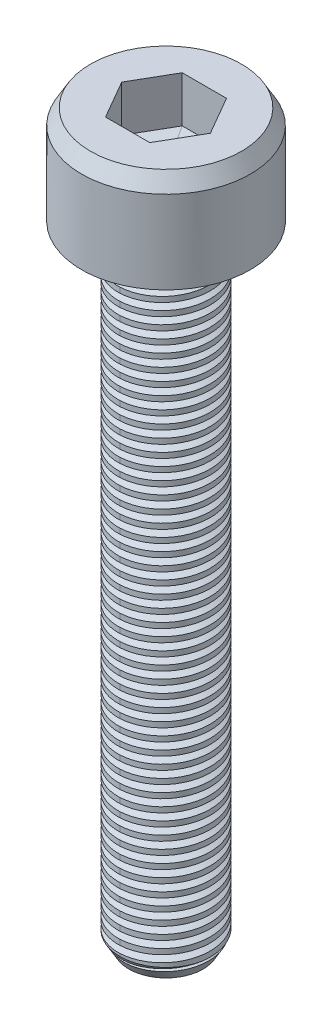
SolidWorks part; units mm, degrees
ref_plane "Front Plane" through (0, 0, 0) normal (0, 0, 1) x (1, 0, 0)
ref_plane "Top Plane" through (0, 0, 0) normal (0, 1, 0) x (1, 0, 0)
ref_plane "Right Plane" through (0, 0, 0) normal (1, 0, 0) x (0, 0, -1)
sketch "Sketch1" plane through (0, 0, 0) normal (0, 1, 0) x (1, 0, 0)
  circle A0 centre (0, 0) radius 2.75
  dimension "D1" = 5.5
extrude "Boss-Extrude1" add sketch "Sketch1" along normal blind 2.7
sketch "Sketch2" plane through (0, 2.7, 0) normal (0, 1, 0) x (1, 0, 0)
  circle A0 centre (0, 0) radius 2.75
  circle A1 centre (0, 0) radius 2.75 construction
  dimension "D1" = 5.5
extrude "Boss-Extrude2" add sketch "Sketch2" along normal blind 0.5 draft 30
sketch "Sketch5" plane through (0, 3.2, 0) normal (0, 1, 0) x (1, 0, 0)
  line L1 (1.4434, 0) -> (0.7217, 1.25)
  line L2 (0.7217, 1.25) -> (-0.7217, 1.25)
  line L3 (-0.7217, 1.25) -> (-1.4434, 0)
  line L4 (-1.4434, 0) -> (-0.7217, -1.25)
  line L5 (-0.7217, -1.25) -> (0.7217, -1.25)
  line L6 (0.7217, -1.25) -> (1.4434, 0)
  circle A0 centre (0, 0) radius 1.25 construction
  circle A1 centre (0, 0) radius 2.4613 construction
  dimension "D1" = 2.5
extrude "Cut-Extrude3" cut sketch "Sketch5" against normal blind 1.5
sketch "Sketch6" plane through (0, 1.7, 0) normal (0, 1, 0) x (1, 0, 0)
  line L0 (1.4434, 0) -> (0.7217, 1.25) construction
  line L1 (1.4434, 0) -> (0.7217, 1.25)
  line L2 (0.7217, 1.25) -> (-0.7217, 1.25)
  line L3 (-0.7217, 1.25) -> (-1.4434, 0)
  line L4 (-1.4434, 0) -> (-0.7217, -1.25)
  line L5 (-0.7217, -1.25) -> (0.7217, -1.25)
  line L6 (0.7217, -1.25) -> (1.4434, 0)
  circle A0 centre (0, 0) radius 1.25 construction
extrude "Cut-Extrude4" cut sketch "Sketch6" against normal blind 0.25 draft 80
sketch "Sketch7" plane through (0, 0, 0) normal (0, -1, 0) x (1, 0, 0)
  circle A0 centre (0, 0) radius 1.5
  circle A1 centre (0, 0) radius 2.75 construction
  dimension "D1" = 3
extrude "Boss-Extrude3" add sketch "Sketch7" along normal blind 20 contours A0
sketch "Sketch8" plane through (0, -20, 0) normal (0, -1, 0) x (1, 0, 0)
  circle A0 centre (0, 0) radius 1.5
  circle A1 centre (0, 0) radius 1.5 construction
  dimension "D1" = 3
extrude "Boss-Extrude4" add sketch "Sketch8" along normal blind 0.5 draft 30
sketch "Sketch9" plane through (0, -20.5, 0) normal (0, -1, 0) x (1, 0, 0)
  circle A0 centre (0, 0) radius 1.5
  circle A1 centre (0, 0) radius 1.2113 construction
  dimension "D1" = 3
curve "Helix/Spiral1" pitch 0.4 height 20 radius 1.5 centre (0, -20.5, 0) axis (0, 1, 0) start towards (1, 0, 0)
sketch "Sketch10" plane through (0, 0, 0) normal (0, 0, 1) x (1, 0, 0)
  line L1 (1.3037, -20.5) -> (1.5981, -20.67)
  line L2 (1.5981, -20.67) -> (1.5981, -20.33)
  line L3 (1.5981, -20.33) -> (1.3037, -20.5)
  circle A0 centre (1.5, -20.5) radius 0.0981 construction
  spline S0 degree 3 poles (1.5, -20.5) (1.5, -20.4917) (1.4219, -20.475) (1.0883, -20.45) (0.589, -20.425) (0, -20.4) (-0.589, -20.375) (-1.0883, -20.35) (-1.4219, -20.325) (-1.5391, -20.3) (-1.4219, -20.275) (-1.0883, -20.25) (-0.589, -20.225) (0, -20.2) (0.589, -20.175) (1.0883, -20.15) (1.4219, -20.125) (1.5391, -20.1) (1.4219, -20.075) (1.0883, -20.05) (0.589, -20.025) (0, -20) (-0.589, -19.975) (-1.0883, -19.95) (-1.4219, -19.925) (-1.5391, -19.9) (-1.4219, -19.875) (-1.0883, -19.85) (-0.589, -19.825) (0, -19.8) (0.589, -19.775) (1.0883, -19.75) (1.4219, -19.725) (1.5391, -19.7) (1.4219, -19.675) (1.0883, -19.65) (0.589, -19.625) (0, -19.6) (-0.589, -19.575) (-1.0883, -19.55) (-1.4219, -19.525) (-1.5391, -19.5) (-1.4219, -19.475) (-1.0883, -19.45) (-0.589, -19.425) (0, -19.4) (0.589, -19.375) (1.0883, -19.35) (1.4219, -19.325) (1.5391, -19.3) (1.4219, -19.275) (1.0883, -19.25) (0.589, -19.225) (0, -19.2) (-0.589, -19.175) (-1.0883, -19.15) (-1.4219, -19.125) (-1.5391, -19.1) (-1.4219, -19.075) (-1.0883, -19.05) (-0.589, -19.025) (0, -19) (0.589, -18.975) (1.0883, -18.95) (1.4219, -18.925) (1.5391, -18.9) (1.4219, -18.875) (1.0883, -18.85) (0.589, -18.825) (0, -18.8) (-0.589, -18.775) (-1.0883, -18.75) (-1.4219, -18.725) (-1.5391, -18.7) (-1.4219, -18.675) (-1.0883, -18.65) (-0.589, -18.625) (0, -18.6) (0.589, -18.575) (1.0883, -18.55) (1.4219, -18.525) (1.5391, -18.5) (1.4219, -18.475) (1.0883, -18.45) (0.589, -18.425) (0, -18.4) (-0.589, -18.375) (-1.0883, -18.35) (-1.4219, -18.325) (-1.5391, -18.3) (-1.4219, -18.275) (-1.0883, -18.25) (-0.589, -18.225) (0, -18.2) (0.589, -18.175) (1.0883, -18.15) (1.4219, -18.125) (1.5391, -18.1) (1.4219, -18.075) (1.0883, -18.05) (0.589, -18.025) (0, -18) (-0.589, -17.975) (-1.0883, -17.95) (-1.4219, -17.925) (-1.5391, -17.9) (-1.4219, -17.875) (-1.0883, -17.85) (-0.589, -17.825) (0, -17.8) (0.589, -17.775) (1.0883, -17.75) (1.4219, -17.725) (1.5391, -17.7) (1.4219, -17.675) (1.0883, -17.65) (0.589, -17.625) (0, -17.6) (-0.589, -17.575) (-1.0883, -17.55) (-1.4219, -17.525) (-1.5391, -17.5) (-1.4219, -17.475) (-1.0883, -17.45) (-0.589, -17.425) (0, -17.4) (0.589, -17.375) (1.0883, -17.35) (1.4219, -17.325) (1.5391, -17.3) (1.4219, -17.275) (1.0883, -17.25) (0.589, -17.225) (0, -17.2) (-0.589, -17.175) (-1.0883, -17.15) (-1.4219, -17.125) (-1.5391, -17.1) (-1.4219, -17.075) (-1.0883, -17.05) (-0.589, -17.025) (0, -17) (0.589, -16.975) (1.0883, -16.95) (1.4219, -16.925) (1.5391, -16.9) (1.4219, -16.875) (1.0883, -16.85) (0.589, -16.825) (0, -16.8) (-0.589, -16.775) (-1.0883, -16.75) (-1.4219, -16.725) (-1.5391, -16.7) (-1.4219, -16.675) (-1.0883, -16.65) (-0.589, -16.625) (0, -16.6) (0.589, -16.575) (1.0883, -16.55) (1.4219, -16.525) (1.5391, -16.5) (1.4219, -16.475) (1.0883, -16.45) (0.589, -16.425) (0, -16.4) (-0.589, -16.375) (-1.0883, -16.35) (-1.4219, -16.325) (-1.5391, -16.3) (-1.4219, -16.275) (-1.0883, -16.25) (-0.589, -16.225) (0, -16.2) (0.589, -16.175) (1.0883, -16.15) (1.4219, -16.125) (1.5391, -16.1) (1.4219, -16.075) (1.0883, -16.05) (0.589, -16.025) (0, -16) (-0.589, -15.975) (-1.0883, -15.95) (-1.4219, -15.925) (-1.5391, -15.9) (-1.4219, -15.875) (-1.0883, -15.85) (-0.589, -15.825) (0, -15.8) (0.589, -15.775) (1.0883, -15.75) (1.4219, -15.725) (1.5391, -15.7) (1.4219, -15.675) (1.0883, -15.65) (0.589, -15.625) (0, -15.6) (-0.589, -15.575) (-1.0883, -15.55) (-1.4219, -15.525) (-1.5391, -15.5) (-1.4219, -15.475) (-1.0883, -15.45) (-0.589, -15.425) (0, -15.4) (0.589, -15.375) (1.0883, -15.35) (1.4219, -15.325) (1.5391, -15.3) (1.4219, -15.275) (1.0883, -15.25) (0.589, -15.225) (0, -15.2) (-0.589, -15.175) (-1.0883, -15.15) (-1.4219, -15.125) (-1.5391, -15.1) (-1.4219, -15.075) (-1.0883, -15.05) (-0.589, -15.025) (0, -15) (0.589, -14.975) (1.0883, -14.95) (1.4219, -14.925) (1.5391, -14.9) (1.4219, -14.875) (1.0883, -14.85) (0.589, -14.825) (0, -14.8) (-0.589, -14.775) (-1.0883, -14.75) (-1.4219, -14.725) (-1.5391, -14.7) (-1.4219, -14.675) (-1.0883, -14.65) (-0.589, -14.625) (0, -14.6) (0.589, -14.575) (1.0883, -14.55) (1.4219, -14.525) (1.5391, -14.5) (1.4219, -14.475) (1.0883, -14.45) (0.589, -14.425) (0, -14.4) (-0.589, -14.375) (-1.0883, -14.35) (-1.4219, -14.325) (-1.5391, -14.3) (-1.4219, -14.275) (-1.0883, -14.25) (-0.589, -14.225) (0, -14.2) (0.589, -14.175) (1.0883, -14.15) (1.4219, -14.125) (1.5391, -14.1) (1.4219, -14.075) (1.0883, -14.05) (0.589, -14.025) (0, -14) (-0.589, -13.975) (-1.0883, -13.95) (-1.4219, -13.925) (-1.5391, -13.9) (-1.4219, -13.875) (-1.0883, -13.85) (-0.589, -13.825) (0, -13.8) (0.589, -13.775) (1.0883, -13.75) (1.4219, -13.725) (1.5391, -13.7) (1.4219, -13.675) (1.0883, -13.65) (0.589, -13.625) (0, -13.6) (-0.589, -13.575) (-1.0883, -13.55) (-1.4219, -13.525) (-1.5391, -13.5) (-1.4219, -13.475) (-1.0883, -13.45) (-0.589, -13.425) (0, -13.4) (0.589, -13.375) (1.0883, -13.35) (1.4219, -13.325) (1.5391, -13.3) (1.4219, -13.275) (1.0883, -13.25) (0.589, -13.225) (0, -13.2) (-0.589, -13.175) (-1.0883, -13.15) (-1.4219, -13.125) (-1.5391, -13.1) (-1.4219, -13.075) (-1.0883, -13.05) (-0.589, -13.025) (0, -13) (0.589, -12.975) (1.0883, -12.95) (1.4219, -12.925) (1.5391, -12.9) (1.4219, -12.875) (1.0883, -12.85) (0.589, -12.825) (0, -12.8) (-0.589, -12.775) (-1.0883, -12.75) (-1.4219, -12.725) (-1.5391, -12.7) (-1.4219, -12.675) (-1.0883, -12.65) (-0.589, -12.625) (0, -12.6) (0.589, -12.575) (1.0883, -12.55) (1.4219, -12.525) (1.5391, -12.5) (1.4219, -12.475) (1.0883, -12.45) (0.589, -12.425) (0, -12.4) (-0.589, -12.375) (-1.0883, -12.35) (-1.4219, -12.325) (-1.5391, -12.3) (-1.4219, -12.275) (-1.0883, -12.25) (-0.589, -12.225) (0, -12.2) (0.589, -12.175) (1.0883, -12.15) (1.4219, -12.125) (1.5391, -12.1) (1.4219, -12.075) (1.0883, -12.05) (0.589, -12.025) (0, -12) (-0.589, -11.975) (-1.0883, -11.95) (-1.4219, -11.925) (-1.5391, -11.9) (-1.4219, -11.875) (-1.0883, -11.85) (-0.589, -11.825) (0, -11.8) (0.589, -11.775) (1.0883, -11.75) (1.4219, -11.725) (1.5391, -11.7) (1.4219, -11.675) (1.0883, -11.65) (0.589, -11.625) (0, -11.6) (-0.589, -11.575) (-1.0883, -11.55) (-1.4219, -11.525) (-1.5391, -11.5) (-1.4219, -11.475) (-1.0883, -11.45) (-0.589, -11.425) (0, -11.4) (0.589, -11.375) (1.0883, -11.35) (1.4219, -11.325) (1.5391, -11.3) (1.4219, -11.275) (1.0883, -11.25) (0.589, -11.225) (0, -11.2) (-0.589, -11.175) (-1.0883, -11.15) (-1.4219, -11.125) (-1.5391, -11.1) (-1.4219, -11.075) (-1.0883, -11.05) (-0.589, -11.025) (0, -11) (0.589, -10.975) (1.0883, -10.95) (1.4219, -10.925) (1.5391, -10.9) (1.4219, -10.875) (1.0883, -10.85) (0.589, -10.825) (0, -10.8) (-0.589, -10.775) (-1.0883, -10.75) (-1.4219, -10.725) (-1.5391, -10.7) (-1.4219, -10.675) (-1.0883, -10.65) (-0.589, -10.625) (0, -10.6) (0.589, -10.575) (1.0883, -10.55) (1.4219, -10.525) (1.5391, -10.5) (1.4219, -10.475) (1.0883, -10.45) (0.589, -10.425) (0, -10.4) (-0.589, -10.375) (-1.0883, -10.35) (-1.4219, -10.325) (-1.5391, -10.3) (-1.4219, -10.275) (-1.0883, -10.25) (-0.589, -10.225) (0, -10.2) (0.589, -10.175) (1.0883, -10.15) (1.4219, -10.125) (1.5391, -10.1) (1.4219, -10.075) (1.0883, -10.05) (0.589, -10.025) (0, -10) (-0.589, -9.975) (-1.0883, -9.95) (-1.4219, -9.925) (-1.5391, -9.9) (-1.4219, -9.875) (-1.0883, -9.85) (-0.589, -9.825) (0, -9.8) (0.589, -9.775) (1.0883, -9.75) (1.4219, -9.725) (1.5391, -9.7) (1.4219, -9.675) (1.0883, -9.65) (0.589, -9.625) (0, -9.6) (-0.589, -9.575) (-1.0883, -9.55) (-1.4219, -9.525) (-1.5391, -9.5) (-1.4219, -9.475) (-1.0883, -9.45) (-0.589, -9.425) (0, -9.4) (0.589, -9.375) (1.0883, -9.35) (1.4219, -9.325) (1.5391, -9.3) (1.4219, -9.275) (1.0883, -9.25) (0.589, -9.225) (0, -9.2) (-0.589, -9.175) (-1.0883, -9.15) (-1.4219, -9.125) (-1.5391, -9.1) (-1.4219, -9.075) (-1.0883, -9.05) (-0.589, -9.025) (0, -9) (0.589, -8.975) (1.0883, -8.95) (1.4219, -8.925) (1.5391, -8.9) (1.4219, -8.875) (1.0883, -8.85) (0.589, -8.825) (0, -8.8) (-0.589, -8.775) (-1.0883, -8.75) (-1.4219, -8.725) (-1.5391, -8.7) (-1.4219, -8.675) (-1.0883, -8.65) (-0.589, -8.625) (0, -8.6) (0.589, -8.575) (1.0883, -8.55) (1.4219, -8.525) (1.5391, -8.5) (1.4219, -8.475) (1.0883, -8.45) (0.589, -8.425) (0, -8.4) (-0.589, -8.375) (-1.0883, -8.35) (-1.4219, -8.325) (-1.5391, -8.3) (-1.4219, -8.275) (-1.0883, -8.25) (-0.589, -8.225) (0, -8.2) (0.589, -8.175) (1.0883, -8.15) (1.4219, -8.125) (1.5391, -8.1) (1.4219, -8.075) (1.0883, -8.05) (0.589, -8.025) (0, -8) (-0.589, -7.975) (-1.0883, -7.95) (-1.4219, -7.925) (-1.5391, -7.9) (-1.4219, -7.875) (-1.0883, -7.85) (-0.589, -7.825) (0, -7.8) (0.589, -7.775) (1.0883, -7.75) (1.4219, -7.725) (1.5391, -7.7) (1.4219, -7.675) (1.0883, -7.65) (0.589, -7.625) (0, -7.6) (-0.589, -7.575) (-1.0883, -7.55) (-1.4219, -7.525) (-1.5391, -7.5) (-1.4219, -7.475) (-1.0883, -7.45) (-0.589, -7.425) (0, -7.4) (0.589, -7.375) (1.0883, -7.35) (1.4219, -7.325) (1.5391, -7.3) (1.4219, -7.275) (1.0883, -7.25) (0.589, -7.225) (0, -7.2) (-0.589, -7.175) (-1.0883, -7.15) (-1.4219, -7.125) (-1.5391, -7.1) (-1.4219, -7.075) (-1.0883, -7.05) (-0.589, -7.025) (0, -7) (0.589, -6.975) (1.0883, -6.95) (1.4219, -6.925) (1.5391, -6.9) (1.4219, -6.875) (1.0883, -6.85) (0.589, -6.825) (0, -6.8) (-0.589, -6.775) (-1.0883, -6.75) (-1.4219, -6.725) (-1.5391, -6.7) (-1.4219, -6.675) (-1.0883, -6.65) (-0.589, -6.625) (0, -6.6) (0.589, -6.575) (1.0883, -6.55) (1.4219, -6.525) (1.5391, -6.5) (1.4219, -6.475) (1.0883, -6.45) (0.589, -6.425) (0, -6.4) (-0.589, -6.375) (-1.0883, -6.35) (-1.4219, -6.325) (-1.5391, -6.3) (-1.4219, -6.275) (-1.0883, -6.25) (-0.589, -6.225) (0, -6.2) (0.589, -6.175) (1.0883, -6.15) (1.4219, -6.125) (1.5391, -6.1) (1.4219, -6.075) (1.0883, -6.05) (0.589, -6.025) (0, -6) (-0.589, -5.975) (-1.0883, -5.95) (-1.4219, -5.925) (-1.5391, -5.9) (-1.4219, -5.875) (-1.0883, -5.85) (-0.589, -5.825) (0, -5.8) (0.589, -5.775) (1.0883, -5.75) (1.4219, -5.725) (1.5391, -5.7) (1.4219, -5.675) (1.0883, -5.65) (0.589, -5.625) (0, -5.6) (-0.589, -5.575) (-1.0883, -5.55) (-1.4219, -5.525) (-1.5391, -5.5) (-1.4219, -5.475) (-1.0883, -5.45) (-0.589, -5.425) (0, -5.4) (0.589, -5.375) (1.0883, -5.35) (1.4219, -5.325) (1.5391, -5.3) (1.4219, -5.275) (1.0883, -5.25) (0.589, -5.225) (0, -5.2) (-0.589, -5.175) (-1.0883, -5.15) (-1.4219, -5.125) (-1.5391, -5.1) (-1.4219, -5.075) (-1.0883, -5.05) (-0.589, -5.025) (0, -5) (0.589, -4.975) (1.0883, -4.95) (1.4219, -4.925) (1.5391, -4.9) (1.4219, -4.875) (1.0883, -4.85) (0.589, -4.825) (0, -4.8) (-0.589, -4.775) (-1.0883, -4.75) (-1.4219, -4.725) (-1.5391, -4.7) (-1.4219, -4.675) (-1.0883, -4.65) (-0.589, -4.625) (0, -4.6) (0.589, -4.575) (1.0883, -4.55) (1.4219, -4.525) (1.5391, -4.5) (1.4219, -4.475) (1.0883, -4.45) (0.589, -4.425) (0, -4.4) (-0.589, -4.375) (-1.0883, -4.35) (-1.4219, -4.325) (-1.5391, -4.3) (-1.4219, -4.275) (-1.0883, -4.25) (-0.589, -4.225) (0, -4.2) (0.589, -4.175) (1.0883, -4.15) (1.4219, -4.125) (1.5391, -4.1) (1.4219, -4.075) (1.0883, -4.05) (0.589, -4.025) (0, -4) (-0.589, -3.975) (-1.0883, -3.95) (-1.4219, -3.925) (-1.5391, -3.9) (-1.4219, -3.875) (-1.0883, -3.85) (-0.589, -3.825) (0, -3.8) (0.589, -3.775) (1.0883, -3.75) (1.4219, -3.725) (1.5391, -3.7) (1.4219, -3.675) (1.0883, -3.65) (0.589, -3.625) (0, -3.6) (-0.589, -3.575) (-1.0883, -3.55) (-1.4219, -3.525) (-1.5391, -3.5) (-1.4219, -3.475) (-1.0883, -3.45) (-0.589, -3.425) (0, -3.4) (0.589, -3.375) (1.0883, -3.35) (1.4219, -3.325) (1.5391, -3.3) (1.4219, -3.275) (1.0883, -3.25) (0.589, -3.225) (0, -3.2) (-0.589, -3.175) (-1.0883, -3.15) (-1.4219, -3.125) (-1.5391, -3.1) (-1.4219, -3.075) (-1.0883, -3.05) (-0.589, -3.025) (0, -3) (0.589, -2.975) (1.0883, -2.95) (1.4219, -2.925) (1.5391, -2.9) (1.4219, -2.875) (1.0883, -2.85) (0.589, -2.825) (0, -2.8) (-0.589, -2.775) (-1.0883, -2.75) (-1.4219, -2.725) (-1.5391, -2.7) (-1.4219, -2.675) (-1.0883, -2.65) (-0.589, -2.625) (0, -2.6) (0.589, -2.575) (1.0883, -2.55) (1.4219, -2.525) (1.5391, -2.5) (1.4219, -2.475) (1.0883, -2.45) (0.589, -2.425) (0, -2.4) (-0.589, -2.375) (-1.0883, -2.35) (-1.4219, -2.325) (-1.5391, -2.3) (-1.4219, -2.275) (-1.0883, -2.25) (-0.589, -2.225) (0, -2.2) (0.589, -2.175) (1.0883, -2.15) (1.4219, -2.125) (1.5391, -2.1) (1.4219, -2.075) (1.0883, -2.05) (0.589, -2.025) (0, -2) (-0.589, -1.975) (-1.0883, -1.95) (-1.4219, -1.925) (-1.5391, -1.9) (-1.4219, -1.875) (-1.0883, -1.85) (-0.589, -1.825) (0, -1.8) (0.589, -1.775) (1.0883, -1.75) (1.4219, -1.725) (1.5391, -1.7) (1.4219, -1.675) (1.0883, -1.65) (0.589, -1.625) (0, -1.6) (-0.589, -1.575) (-1.0883, -1.55) (-1.4219, -1.525) (-1.5391, -1.5) (-1.4219, -1.475) (-1.0883, -1.45) (-0.589, -1.425) (0, -1.4) (0.589, -1.375) (1.0883, -1.35) (1.4219, -1.325) (1.5391, -1.3) (1.4219, -1.275) (1.0883, -1.25) (0.589, -1.225) (0, -1.2) (-0.589, -1.175) (-1.0883, -1.15) (-1.4219, -1.125) (-1.5391, -1.1) (-1.4219, -1.075) (-1.0883, -1.05) (-0.589, -1.025) (0, -1) (0.589, -0.975) (1.0883, -0.95) (1.4219, -0.925) (1.5391, -0.9) (1.4219, -0.875) (1.0883, -0.85) (0.589, -0.825) (0, -0.8) (-0.589, -0.775) (-1.0883, -0.75) (-1.4219, -0.725) (-1.5391, -0.7) (-1.4219, -0.675) (-1.0883, -0.65) (-0.589, -0.625) (0, -0.6) (0.589, -0.575) (1.0883, -0.55) (1.4219, -0.525) (1.5, -0.5083) (1.5, -0.5) knots 0 0 0 0 0.00125 0.0025 0.00375 0.005 0.00625 0.0075 0.00875 0.01 0.01125 0.0125 0.01375 0.015 0.01625 0.0175 0.01875 0.02 0.02125 0.0225 0.02375 0.025 0.02625 0.0275 0.02875 0.03 0.03125 0.0325 0.03375 0.035 0.03625 0.0375 0.03875 0.04 0.04125 0.0425 0.04375 0.045 0.04625 0.0475 0.04875 0.05 0.05125 0.0525 0.05375 0.055 0.05625 0.0575 0.05875 0.06 0.06125 0.0625 0.06375 0.065 0.06625 0.0675 0.06875 0.07 0.07125 0.0725 0.07375 0.075 0.07625 0.0775 0.07875 0.08 0.08125 0.0825 0.08375 0.085 0.08625 0.0875 0.08875 0.09 0.09125 0.0925 0.09375 0.095 0.09625 0.0975 0.09875 0.1 0.10125 0.1025 0.10375 0.105 0.10625 0.1075 0.10875 0.11 0.11125 0.1125 0.11375 0.115 0.11625 0.1175 0.11875 0.12 0.12125 0.1225 0.12375 0.125 0.12625 0.1275 0.12875 0.13 0.13125 0.1325 0.13375 0.135 0.13625 0.1375 0.13875 0.14 0.14125 0.1425 0.14375 0.145 0.14625 0.1475 0.14875 0.15 0.15125 0.1525 0.15375 0.155 0.15625 0.1575 0.15875 0.16 0.16125 0.1625 0.16375 0.165 0.16625 0.1675 0.16875 0.17 0.17125 0.1725 0.17375 0.175 0.17625 0.1775 0.17875 0.18 0.18125 0.1825 0.18375 0.185 0.18625 0.1875 0.18875 0.19 0.19125 0.1925 0.19375 0.195 0.19625 0.1975 0.19875 0.2 0.20125 0.2025 0.20375 0.205 0.20625 0.2075 0.20875 0.21 0.21125 0.2125 0.21375 0.215 0.21625 0.2175 0.21875 0.22 0.22125 0.2225 0.22375 0.225 0.22625 0.2275 0.22875 0.23 0.23125 0.2325 0.23375 0.235 0.23625 0.2375 0.23875 0.24 0.24125 0.2425 0.24375 0.245 0.24625 0.2475 0.24875 0.25 0.25125 0.2525 0.25375 0.255 0.25625 0.2575 0.25875 0.26 0.26125 0.2625 0.26375 0.265 0.26625 0.2675 0.26875 0.27 0.27125 0.2725 0.27375 0.275 0.27625 0.2775 0.27875 0.28 0.28125 0.2825 0.28375 0.285 0.28625 0.2875 0.28875 0.29 0.29125 0.2925 0.29375 0.295 0.29625 0.2975 0.29875 0.3 0.30125 0.3025 0.30375 0.305 0.30625 0.3075 0.30875 0.31 0.31125 0.3125 0.31375 0.315 0.31625 0.3175 0.31875 0.32 0.32125 0.3225 0.32375 0.325 0.32625 0.3275 0.32875 0.33 0.33125 0.3325 0.33375 0.335 0.33625 0.3375 0.33875 0.34 0.34125 0.3425 0.34375 0.345 0.34625 0.3475 0.34875 0.35 0.35125 0.3525 0.35375 0.355 0.35625 0.3575 0.35875 0.36 0.36125 0.3625 0.36375 0.365 0.36625 0.3675 0.36875 0.37 0.37125 0.3725 0.37375 0.375 0.37625 0.3775 0.37875 0.38 0.38125 0.3825 0.38375 0.385 0.38625 0.3875 0.38875 0.39 0.39125 0.3925 0.39375 0.395 0.39625 0.3975 0.39875 0.4 0.40125 0.4025 0.40375 0.405 0.40625 0.4075 0.40875 0.41 0.41125 0.4125 0.41375 0.415 0.41625 0.4175 0.41875 0.42 0.42125 0.4225 0.42375 0.425 0.42625 0.4275 0.42875 0.43 0.43125 0.4325 0.43375 0.435 0.43625 0.4375 0.43875 0.44 0.44125 0.4425 0.44375 0.445 0.44625 0.4475 0.44875 0.45 0.45125 0.4525 0.45375 0.455 0.45625 0.4575 0.45875 0.46 0.46125 0.4625 0.46375 0.465 0.46625 0.4675 0.46875 0.47 0.47125 0.4725 0.47375 0.475 0.47625 0.4775 0.47875 0.48 0.48125 0.4825 0.48375 0.485 0.48625 0.4875 0.48875 0.49 0.49125 0.4925 0.49375 0.495 0.49625 0.4975 0.49875 0.5 0.50125 0.5025 0.50375 0.505 0.50625 0.5075 0.50875 0.51 0.51125 0.5125 0.51375 0.515 0.51625 0.5175 0.51875 0.52 0.52125 0.5225 0.52375 0.525 0.52625 0.5275 0.52875 0.53 0.53125 0.5325 0.53375 0.535 0.53625 0.5375 0.53875 0.54 0.54125 0.5425 0.54375 0.545 0.54625 0.5475 0.54875 0.55 0.55125 0.5525 0.55375 0.555 0.55625 0.5575 0.55875 0.56 0.56125 0.5625 0.56375 0.565 0.56625 0.5675 0.56875 0.57 0.57125 0.5725 0.57375 0.575 0.57625 0.5775 0.57875 0.58 0.58125 0.5825 0.58375 0.585 0.58625 0.5875 0.58875 0.59 0.59125 0.5925 0.59375 0.595 0.59625 0.5975 0.59875 0.6 0.60125 0.6025 0.60375 0.605 0.60625 0.6075 0.60875 0.61 0.61125 0.6125 0.61375 0.615 0.61625 0.6175 0.61875 0.62 0.62125 0.6225 0.62375 0.625 0.62625 0.6275 0.62875 0.63 0.63125 0.6325 0.63375 0.635 0.63625 0.6375 0.63875 0.64 0.64125 0.6425 0.64375 0.645 0.64625 0.6475 0.64875 0.65 0.65125 0.6525 0.65375 0.655 0.65625 0.6575 0.65875 0.66 0.66125 0.6625 0.66375 0.665 0.66625 0.6675 0.66875 0.67 0.67125 0.6725 0.67375 0.675 0.67625 0.6775 0.67875 0.68 0.68125 0.6825 0.68375 0.685 0.68625 0.6875 0.68875 0.69 0.69125 0.6925 0.69375 0.695 0.69625 0.6975 0.69875 0.7 0.70125 0.7025 0.70375 0.705 0.70625 0.7075 0.70875 0.71 0.71125 0.7125 0.71375 0.715 0.71625 0.7175 0.71875 0.72 0.72125 0.7225 0.72375 0.725 0.72625 0.7275 0.72875 0.73 0.73125 0.7325 0.73375 0.735 0.73625 0.7375 0.73875 0.74 0.74125 0.7425 0.74375 0.745 0.74625 0.7475 0.74875 0.75 0.75125 0.7525 0.75375 0.755 0.75625 0.7575 0.75875 0.76 0.76125 0.7625 0.76375 0.765 0.76625 0.7675 0.76875 0.77 0.77125 0.7725 0.77375 0.775 0.77625 0.7775 0.77875 0.78 0.78125 0.7825 0.78375 0.785 0.78625 0.7875 0.78875 0.79 0.79125 0.7925 0.79375 0.795 0.79625 0.7975 0.79875 0.8 0.80125 0.8025 0.80375 0.805 0.80625 0.8075 0.80875 0.81 0.81125 0.8125 0.81375 0.815 0.81625 0.8175 0.81875 0.82 0.82125 0.8225 0.82375 0.825 0.82625 0.8275 0.82875 0.83 0.83125 0.8325 0.83375 0.835 0.83625 0.8375 0.83875 0.84 0.84125 0.8425 0.84375 0.845 0.84625 0.8475 0.84875 0.85 0.85125 0.8525 0.85375 0.855 0.85625 0.8575 0.85875 0.86 0.86125 0.8625 0.86375 0.865 0.86625 0.8675 0.86875 0.87 0.87125 0.8725 0.87375 0.875 0.87625 0.8775 0.87875 0.88 0.88125 0.8825 0.88375 0.885 0.88625 0.8875 0.88875 0.89 0.89125 0.8925 0.89375 0.895 0.89625 0.8975 0.89875 0.9 0.90125 0.9025 0.90375 0.905 0.90625 0.9075 0.90875 0.91 0.91125 0.9125 0.91375 0.915 0.91625 0.9175 0.91875 0.92 0.92125 0.9225 0.92375 0.925 0.92625 0.9275 0.92875 0.93 0.93125 0.9325 0.93375 0.935 0.93625 0.9375 0.93875 0.94 0.94125 0.9425 0.94375 0.945 0.94625 0.9475 0.94875 0.95 0.95125 0.9525 0.95375 0.955 0.95625 0.9575 0.95875 0.96 0.96125 0.9625 0.96375 0.965 0.96625 0.9675 0.96875 0.97 0.97125 0.9725 0.97375 0.975 0.97625 0.9775 0.97875 0.98 0.98125 0.9825 0.98375 0.985 0.98625 0.9875 0.98875 0.99 0.99125 0.9925 0.99375 0.995 0.99625 0.9975 0.99875 1 1 1 1 construction
  dimension "D1" = 0.1963
  dimension "D2" = 1.3037
sweep "Cut-Sweep1" cut profiles "Sketch10" path "Helix/Spiral1" align with end faces yes
